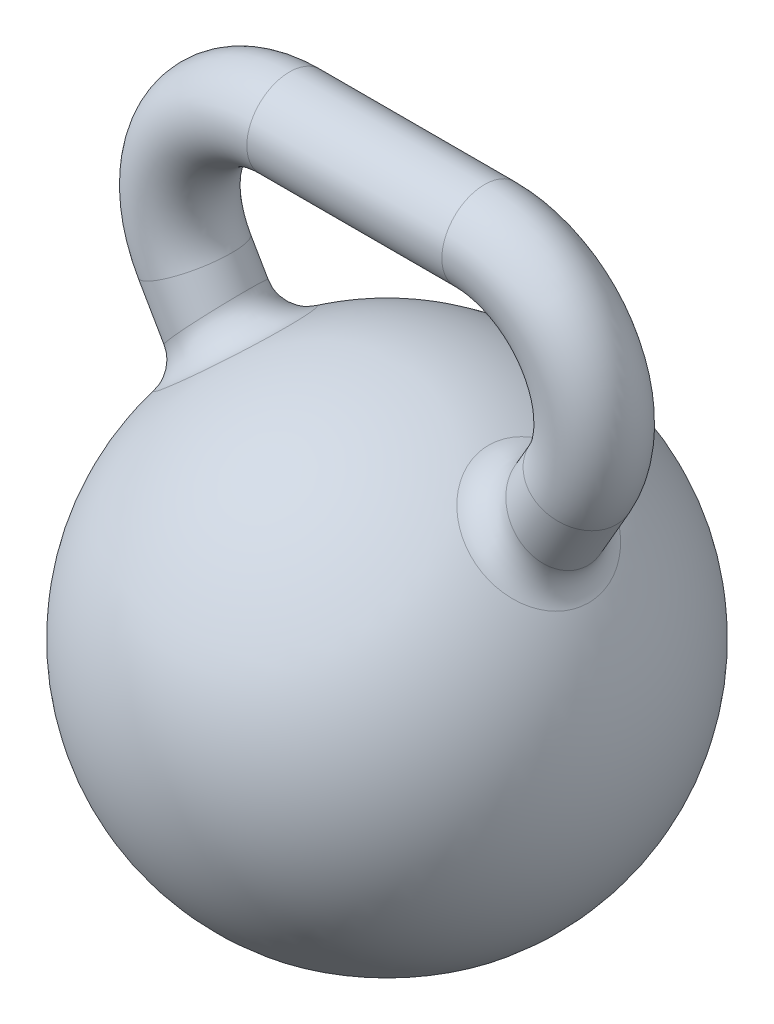
SolidWorks part; units mm, degrees
ref_plane "Front Plane" through (0, 0, 0) normal (0, 0, 1) x (1, 0, 0)
ref_plane "Top Plane" through (0, 0, 0) normal (0, 1, 0) x (1, 0, 0)
ref_plane "Right Plane" through (0, 0, 0) normal (1, 0, 0) x (0, 0, -1)
sketch "Sketch1" plane through (0, 0, 0) normal (0, 0, 1) x (1, 0, 0)
  line L0 (-63.7535, -77.47) -> (63.7535, -77.47)
  line L1 (0, 0) -> (0, -31.4594) construction
  line L2 (0, 100.33) -> (0, -77.47)
  arc A0 (63.7535, -77.47) -> (-63.7535, -77.47) centre (0, 0) ccw
  dimension "D1" = 200.66
  dimension "D2" = 77.47
revolve "Revolve1" add sketch "Sketch1" angle 360 about L2 region at (-43.8093, 5.83, 0)
sketch "Sketch2" plane through (0, 0, 0) normal (0, 0, 1) x (1, 0, 0)
  line L0 (0, 0) -> (0, 184.15) construction
  line L1 (79.5811, 61.0979) -> (95.6326, 88.9)
  line L3 (-63.7535, -77.47) -> (63.7535, -77.47) construction
  line L4 (-79.5811, 61.0979) -> (-95.6326, 88.9)
  line L5 (-40.64, 184.15) -> (40.64, 184.15)
  line L7 (-79.5811, 61.0979) -> (-50.8974, 11.4163)
  line L8 (79.5811, 61.0979) -> (54.3851, 17.4571)
  arc A0 (-95.6326, 88.9) -> (-40.64, 184.15) centre (-40.64, 120.65) cw
  arc A1 (95.6326, 88.9) -> (40.64, 184.15) centre (40.64, 120.65) ccw
  arc A3 (79.5811, 61.0979) -> (-79.5811, 61.0979) centre (0, 0) ccw construction
  point P0 (0, 0)
  dimension "D3" = 63.5
  dimension "D6" = 100.33
  dimension "D1" = 77.47
  dimension "D2" = 60
  dimension "D4" = 81.28
  dimension "D5" = 261.62
ref_plane "Plane1" through (-50.8974, 11.4163, 0) normal (0.5, -0.866, 0) x (-0.866, -0.5, 0)
sketch "Sketch3" plane through (-50.8974, 11.4163, 0) normal (0.5, -0.866, 0) x (-0.866, -0.5, 0)
  line L2 (0, 0) -> (0, 20.8941) construction
  circle A0 centre (-17.78, 0) radius 17.78
  point P2 (0, 0)
  dimension "D1" = 35.56
sweep "Sweep1" add profiles "Sketch3" path "Sketch2"
fillet "Fillet1" radius 12.7 2 edges at (77.9604, 62.5826, 8.4678) (-53.45, 84.6755, 6.2667)
